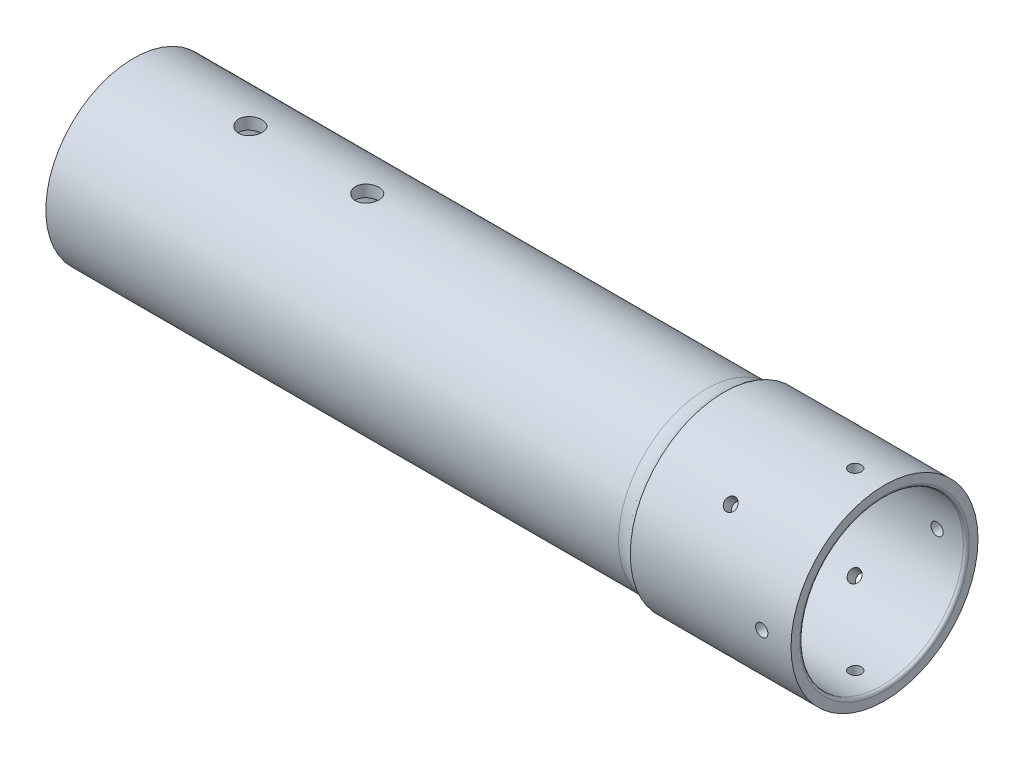
SolidWorks part; units mm, degrees
material "Д16Т  ГОСТ 13616-97"
ref_plane "Спереди" through (0, 0, 0) normal (0, 0, 1) x (1, 0, 0)
ref_plane "Сверху" through (0, 0, 0) normal (0, 1, 0) x (1, 0, 0)
ref_plane "Справа" through (0, 0, 0) normal (1, 0, 0) x (0, 0, -1)
sketch "Эскиз1" plane through (0, 0, 0) normal (1, 0, 0) x (0, 0, -1)
  circle A0 centre (0, 0) radius 30
  circle A1 centre (0, 0) radius 26
  dimension "D1" = 60
  dimension "D2" = 4
extrude "Бобышка-Вытянуть1" add sketch "Эскиз1" along normal blind 257
sketch "Sketch2" plane through (257, 0, 0) normal (1, 0, 0) x (0, 0, -1)
  circle A1 centre (0, 0) radius 30
  circle A2 centre (0, 0) radius 30
  dimension "D1" = 0
extrude "Extrude-Thin1" add sketch "Sketch2" against normal blind 55 thin thin type one direction wall 2
sketch "Эскиз2" plane through (0, 0, 0) normal (0, 1, 0) x (1, 0, 0)
  line L0 (0, 30) -> (0, -30) construction
  circle A0 centre (40, 0) radius 4
  circle A1 centre (80, 0) radius 4
  dimension "D1" = 8
  dimension "D2" = 80
  dimension "D3" = 40
extrude "Вырез-Вытянуть1" cut sketch "Эскиз2" along normal through all
sketch "Эскиз3" plane through (0, 0, 0) normal (0, 1, 0) x (1, 0, 0)
  line L0 (257, -30) -> (257, 30) construction
  circle A0 centre (247, 0) radius 2.1
  dimension "D1" = 4.2
  dimension "D2" = 10
extrude "Вырез-Вытянуть2" cut sketch "Эскиз3" along normal up to next
ref_axis "Ось1" through (257, 0, 0) along (-1, 0, 0)
ref_plane "Плоскость1" through (0, 0, 0) normal (0, 0.7071, -0.7071) x (-1, 0, 0)
sketch "Эскиз4" plane through (0, 0, 0) normal (0, 0.7071, -0.7071) x (-1, 0, 0)
  line L0 (-257, 30) -> (-257, -30) construction
  circle A0 centre (-227, 0) radius 2.1
  dimension "D1" = 4.2
  dimension "D2" = 30
extrude "Вырез-Вытянуть3" cut sketch "Эскиз4" along normal up to next
pattern_circular "Круговой массив1" count 4 over 360 about axis through (257, 0, 0) along (-1, 0, 0) of "Вырез-Вытянуть2", "Вырез-Вытянуть3"
sketch "Sketch1" plane through (257, 0, 0) normal (1, 0, 0) x (0, 0, -1)
  circle A0 centre (0, 0) radius 28
  circle A1 centre (0, 0) radius 26
extrude "Cut-Extrude1" cut sketch "Sketch1" against normal blind 43
fillet "Fillet1" radius 1 1 edges at (214, 0, -28)
fillet "Fillet2" radius 10 1 edges at (202, 0, -30)
fillet "Fillet3" radius 1 1 edges at (257, 0, -28)
